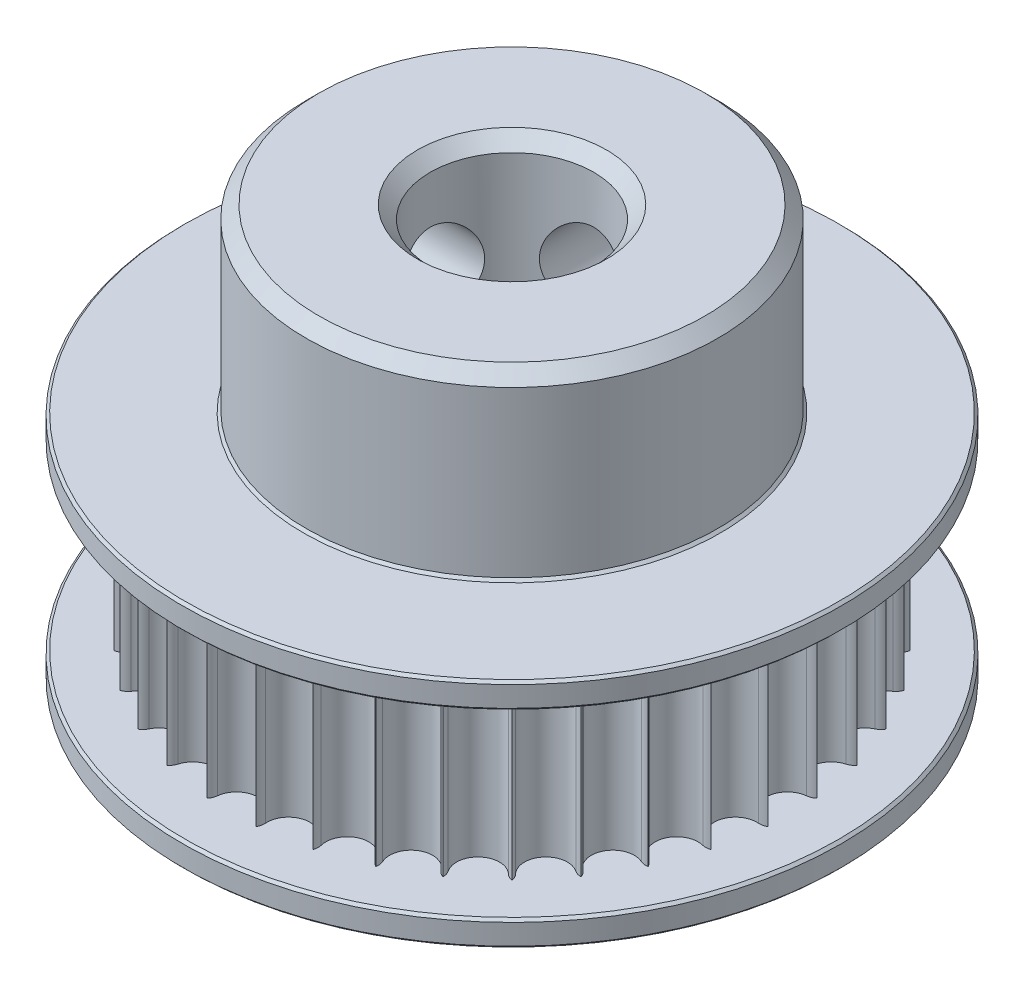
SolidWorks part; units mm, degrees
ref_plane "Front plan" through (0, 0, 0) normal (0, 0, 1) x (1, 0, 0)
ref_plane "Top plan" through (0, 0, 0) normal (0, 1, 0) x (1, 0, 0)
ref_plane "Right plan" through (0, 0, 0) normal (1, 0, 0) x (0, 0, -1)
sketch "Skica2" plane through (0, 0, 0) normal (0, 0, 1) x (1, 0, 0)
  line L0 (8, 8.5) -> (3.175, 8.5)
  line L1 (3.175, 8.5) -> (3.175, -8.5)
  line L2 (3.175, -8.5) -> (6.11, -8.5)
  line L3 (0, -8.5) -> (0, 8.5) construction
  line L4 (0, 8.5) -> (3.175, 8.5)
  line L5 (0, -8.5) -> (3.175, -8.5)
  line L6 (6.11, -8.5) -> (6.11, -7.5)
  line L7 (12.8, 0.5) -> (11.15, 0.5)
  line L8 (11.15, 0.5) -> (11.15, -6.5)
  line L9 (12.8, 0.5) -> (12.8, 1.5)
  line L12 (12.8, -7.5) -> (6.11, -7.5)
  line L13 (12.8, 1.5) -> (8, 1.5)
  line L14 (12.8, -7.5) -> (12.8, -6.5)
  line L15 (11.15, -6.5) -> (12.8, -6.5)
  line L16 (8, 1.5) -> (8, 8.5)
  point P6 (9.455, -7.5)
  point P7 (0, 0)
  dimension "D2" = 1
  dimension "D6" = 25.6
  dimension "D3" = 22.3
  dimension "D1" = 6.35
  dimension "D8" = 17
  dimension "D4" = 1
  dimension "D7" = 16
  dimension "D9" = 7
revolve "Revolute" add sketch "Skica2" angle 360 about L3 region at (6.7625, -0.7141, 0)
sketch "Sketch2" plane through (0, 0.5, 0) normal (0, -1, 0) x (1, 0, 0)
  line L0 (0, 0) -> (0, 10.7023) construction
  line L1 (0, 0) -> (3.7597, 10.497) construction
  line L3 (0, 0) -> (-2.1589, 10.939) construction
  circle A1 centre (0, 0) radius 9.8663 construction
  circle A2 centre (0, 0) radius 10.65 construction
  arc A3 (-0.8317, 10.6175) -> (0.8317, 10.6175) centre (0, 10.7023) ccw
  arc A7 (-1.3915, 11.0628) -> (-2.1589, 10.939) centre (0, 0) ccw
  arc A8 (0, 12.5893) -> (2.1589, 10.939) centre (0.5977, 11.134) cw
  circle A9 centre (0, 0) radius 11.15 construction
  arc A10 (1.3915, 11.0628) -> (2.1589, 10.939) centre (0, 0) cw
  arc A11 (1.3915, 11.0628) -> (0.8317, 10.6175) centre (1.3291, 10.5667) ccw
  arc A12 (0, 12.5893) -> (-2.1589, 10.939) centre (-0.5977, 11.134) ccw
  arc A13 (-1.3915, 11.0628) -> (-0.8317, 10.6175) centre (-1.3291, 10.5667) cw
  point P0 (0, 0)
  circle M8 centre (0, 0) radius 11.15
  dimension "D2" = 1
  dimension "D4" = 0.836
  dimension "D6" = 22.3
  dimension "D3" = 1.5733
  dimension "D1" = 0.5
extrude "Cut-Extrude1" cut sketch "Sketch2" along normal up to surface (7 mm away) contours A8 M8 | A11 A3 M8 region at (0, 0.5, 10.6043) region at (0, 0.5, 11.8034) up to face at (12.8, -6.5, 0)
pattern_circular "CirPattern1" count 36 over 360 about axis through (0, -8.5, 0) along (0, -1, 0) of "Cut-Extrude1" reverse direction yes
sketch "Sketch3" plane through (0, 0, 0) normal (1, 0, 0) x (0, 0, -1)
  line L0 (0, 8.5) -> (0, 0.5) construction
  line L1 (3.175, 8.5) -> (-3.175, 8.5) construction
  circle A0 centre (0, 4.5) radius 1.65
  dimension "D1" = 3.3
extrude "Cut-Extrude2" cut sketch "Sketch3" against normal up to next
sketch "Sketch4" plane through (0, 0, 0) normal (0, 0, 1) x (1, 0, 0)
  line L0 (0, 8.5) -> (0, 0.5) construction
  line L1 (12.8, 8.5) -> (-12.8, 8.5) construction
  line L2 (-0.8317, 0.5) -> (0.8317, 0.5) construction
  circle A0 centre (0, 4.5) radius 1.65
  dimension "D1" = 3.3
extrude "Cut-Extrude3" cut sketch "Sketch4" against normal up to next
chamfer "Chamfer1" distance 1 angle 45 1 edges at (6.11, -7.5, 0)
chamfer "Chamfer2" distance 0.5 angle 45 2 edges at (8, 8.5, 0) (3.175, 8.5, 0)
chamfer "Chamfer3" distance 0.1 angle 45 5 edges at (12.8, -7.5, 0) (12.8, -6.5, 0) (12.8, 0.5, 0) (12.8, 1.5, 0) (8, 1.5, 0)
equation "\"`\"=2"
equation "\"D6@Sketch2\"= \"D3@Skica2\""
